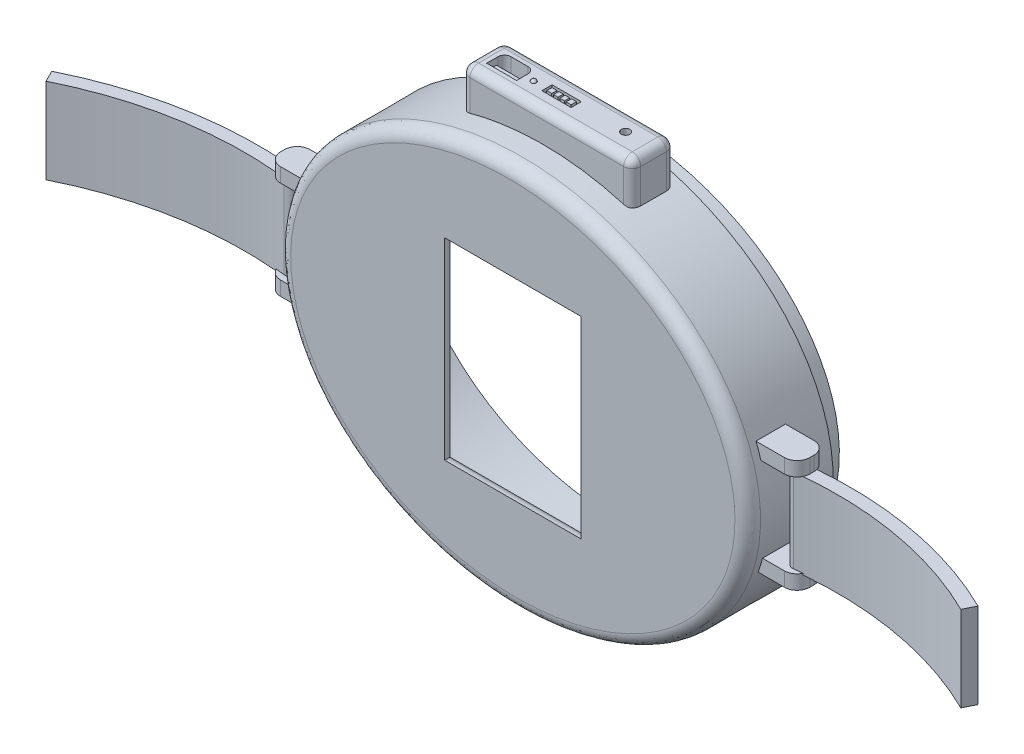
SolidWorks part; units mm, degrees
material "ABS"
ref_plane "Plan de face" through (0, 0, 0) normal (0, 0, 1) x (1, 0, 0)
ref_plane "Plan de dessus" through (0, 0, 0) normal (0, 1, 0) x (1, 0, 0)
ref_plane "Plan de droite" through (0, 0, 0) normal (1, 0, 0) x (0, 0, -1)
sketch "Esquisse1" plane through (0, 0, 0) normal (0, 0, 1) x (1, 0, 0)
  ellipse E0 centre (0, 0) end of major axis (55, -2.2067) minor radius 45.0362
  dimension "D1" = 110
  dimension "D2" = 90
extrude "Boss.-Extru.1" add sketch "Esquisse1" along normal blind 20
sketch "Esquisse2" plane through (0, 0, 0) normal (0, 0, -1) x (-1, 0, 0)
  ellipse E0 centre (0, 0) end of major axis (49.5, 0) minor radius 39.5
  dimension "D1" = 99
  dimension "D2" = 79
extrude "Enlèv. mat.-Extru.1" cut sketch "Esquisse2" against normal blind 17
sketch "Esquisse4" plane through (0, 0, 0) normal (0, 0, -1) x (-1, 0, 0)
  ellipse E0 centre (0, 0) end of major axis (49.5, 0) minor radius 39.5
  ellipse E1 centre (0, 0) end of major axis (49.5, 0) minor radius 39.5 construction
  ellipse E2 centre (0, 0) end of major axis (51.5, 0) minor radius 41.5
  dimension "D1" = 83
  dimension "D2" = 103
extrude "Boss.-Extru.2" add sketch "Esquisse4" along normal blind 5
sketch "Esquisse5" plane through (0, 0, 17) normal (0, 0, -1) x (-1, 0, 0)
  line L0 (-78.8633, 0) -> (101.9973, 0) construction
  line L1 (-15.9471, 22.5665) -> (15.9471, 22.5665)
  line L2 (-15.9471, 22.5665) -> (-15.9471, -22.5665)
  line L3 (-15.9471, -22.5665) -> (15.9471, -22.5665)
  line L4 (15.9471, 22.5665) -> (15.9471, -22.5665)
  line L5 (-15.9471, 22.5665) -> (15.9471, -22.5665) construction
  line L6 (-15.9471, -22.5665) -> (15.9471, 22.5665) construction
  point P0 (0, 0)
ref_plane "Plan1" through (0, -47.5, 0) normal (0, 1, 0) x (1, 0, 0)
ref_plane "Plan2" through (62, 0, 0) normal (1, 0, 0) x (0, 0, -1)
sketch "Esquisse7" plane through (62, 0, 0) normal (1, 0, 0) x (0, 0, -1)
  line L0 (0, 0) -> (-49.6576, 0) construction
  line L1 (-8.4829, -13.1626) -> (-15.4028, -13.1626)
  line L2 (-8.4829, -13.1626) -> (-8.4829, -9.8236)
  line L3 (-8.4829, -9.8236) -> (-15.4028, -9.8236)
  line L4 (-15.4028, -13.1626) -> (-15.4028, -9.8236)
  line L5 (-15.4028, 13.1626) -> (-15.4028, 9.8236)
  line L6 (-8.4829, 13.1626) -> (-15.4028, 13.1626)
  line L7 (-8.4829, 13.1626) -> (-8.4829, 9.8236)
  line L8 (-8.4829, 9.8236) -> (-15.4028, 9.8236)
extrude "Boss.-Extru.3" add sketch "Esquisse7" against normal blind 10
fillet "Congé2" radius 3 4 edges at (62, 11.4931, 15.4028) (62, 11.4931, 8.4829) (62, -11.4931, 8.4829) (62, -11.4931, 15.4028)
sketch "Esquisse8" plane through (0, 13.1626, 0) normal (0, 1, 0) x (1, 0, 0)
  line L0 (62, -11.9429) -> (50.9958, -11.9429) construction
  line L1 (62, -11.4829) -> (62, -12.4028) construction
  circle A1 centre (59.2821, -11.9429) radius 1
  dimension "D1" = 2
extrude "Boss.-Extru.4" add sketch "Esquisse8" against normal blind 25
mirror "Symétrie1" about plane through (0, 0, 0) normal (1, 0, 0) of "Boss.-Extru.4", "Boss.-Extru.3", "Congé2"
sketch "Esquisse9" plane through (0, 9.8236, 0) normal (0, -1, 0) x (-1, 0, 0)
  line L0 (-108.4769, -19.5088) -> (-107.145, -22.197)
  arc A0 (-59.2821, -10.9429) -> (-108.4769, -19.5088) centre (-69.4021, -98.3701) ccw
  circle A1 centre (-59.2821, -11.9429) radius 1 construction
  arc A2 (-59.627, -13.923) -> (-107.145, -22.197) centre (-69.4021, -98.3701) ccw
  arc A3 (-59.627, -13.923) -> (-59.2821, -10.9429) centre (-59.4546, -12.4329) ccw
  dimension "D1" = 3
extrude "Boss.-Extru.5" add sketch "Esquisse9" along normal blind 20
mirror "Symétrie2" about plane through (0, 0, 0) normal (1, 0, 0) of "Boss.-Extru.5"
extrude "Enlèv. mat.-Extru.2" cut sketch "Esquisse5" against normal through all
fillet "Congé3" radius 3 1 edges at (-49.5, 0, 17)
fillet "Congé4" radius 3 1 edges at (55, -2.2067, 20)
fillet "Congé5" radius 3 4 edges at (0, -22.5665, 17) (-15.9471, 0, 17) (15.9471, 0, 17) (0, 22.5665, 17)
ref_plane "Plan3" through (0, 52, 0) normal (0, 1, 0) x (1, 0, 0)
sketch "Esquisse10" plane through (0, 52, 0) normal (0, 1, 0) x (1, 0, 0)
  line L0 (0, 29.0079) -> (0, -90.2476) construction
  line L1 (-20, -12.029) -> (20, -12.029)
  line L2 (-20, -12.029) -> (-20, -2.029)
  line L3 (-20, -2.029) -> (20, -2.029)
  line L4 (20, -12.029) -> (20, -2.029)
  line L5 (-20, -12.029) -> (20, -2.029) construction
  line L6 (-20, -2.029) -> (20, -12.029) construction
  point P0 (0, -7.029)
  dimension "D1" = 40
  dimension "D2" = 10
extrude "Boss.-Extru.6" add sketch "Esquisse10" against normal blind 10
fillet "Congé8" radius 2 8 edges at (0, 52, 12.029) (20, 47, 12.029) (20, 52, 7.029) (20, 47, 2.029) (0, 52, 2.029) (-20, 52, 7.029) (-20, 47.1163, 12.029) (-20, 47.1163, 2.029)
sketch "Esquisse11" plane through (0, 52, 0) normal (0, 1, 0) x (1, 0, 0)
  line L0 (-18, -7.029) -> (22.5805, -7.029) construction
  line L1 (-18, -4.029) -> (-18, -10.029) construction
  line L3 (-17.0041, -4.9423) -> (-10.0041, -4.9423)
  line L4 (-17.0041, -4.9423) -> (-17.0041, -9.1156)
  line L5 (-17.0041, -9.1156) -> (-10.0041, -9.1156)
  line L6 (-10.0041, -4.9423) -> (-10.0041, -9.1156)
  line L7 (-17.0041, -4.9423) -> (-10.0041, -9.1156) construction
  line L8 (-17.0041, -9.1156) -> (-10.0041, -4.9423) construction
  point P4 (-13.5041, -7.029)
  dimension "D1" = 7
extrude "Enlèv. mat.-Extru.3" cut sketch "Esquisse11" against normal blind 6
sketch "Esquisse12" plane through (0, 46, 0) normal (0, 1, 0) x (1, 0, 0)
  line L0 (-17.0041, -9.1156) -> (-10.0041, -9.1156) construction
  line L1 (-10.4458, -7.3727) -> (-16.4605, -7.3727)
  line L2 (-10.4458, -7.3727) -> (-10.4458, -9.1156)
  line L3 (-10.4458, -9.1156) -> (-16.4605, -9.1156)
  line L4 (-16.4605, -7.3727) -> (-16.4605, -9.1156)
extrude "Boss.-Extru.7" add sketch "Esquisse12" along normal blind 5
sketch "Esquisse13" plane through (0, 0, 7.3727) normal (0, 0, -1) x (-1, 0, 0)
  line L0 (10.4458, 46) -> (16.4605, 46) construction
  line L1 (13.888, 46) -> (13.0092, 46)
  line L2 (13.888, 46) -> (13.888, 50.6099)
  line L4 (13.0092, 46) -> (13.0092, 50.6099)
  line L7 (11.9961, 46) -> (11.1216, 46)
  line L8 (11.9961, 46) -> (11.9961, 50.6099)
  line L10 (11.1216, 46) -> (11.1216, 50.6099)
  line L11 (14.9026, 46) -> (15.7847, 46)
  line L12 (14.9026, 46) -> (14.9026, 50.6099)
  line L14 (15.7847, 46) -> (15.7847, 50.6099)
  line L17 (15.7847, 50.6099) -> (14.9026, 50.6099)
  line L18 (13.888, 50.6099) -> (13.0092, 50.6099)
  line L19 (11.9961, 50.6099) -> (11.1216, 50.6099)
  point P9 (0, 0)
  point P10 (0, 0)
  point P16 (14.9026, 50.6099)
  point P18 (15.7847, 50.8113)
  point P19 (13.888, 50.6099)
  point P20 (13.0092, 50.6099)
  point P21 (11.9961, 50.6099)
  point P22 (11.1216, 51)
extrude "Boss.-Extru.8" add sketch "Esquisse13" along normal blind 0.5
chamfer "Chanfrein2" distance 2 angle 45 3 edges at (-11.5588, 50.6099, 6.8727) (-13.4486, 50.6099, 6.8727) (-15.3436, 50.6099, 6.8727)
fillet "Congé9" radius 1.5 2 edges at (-10.0041, 49, 4.9423) (-17.0041, 49, 4.9423)
sketch "Esquisse14" plane through (0, 52, 0) normal (0, 1, 0) x (1, 0, 0)
  line L0 (18, -7.029) -> (1.3064, -7.029) construction
  line L1 (-4.9633, -5.8292) -> (1.8764, -5.8292)
  line L2 (-4.9633, -5.8292) -> (-4.9633, -8.2288)
  line L3 (-4.9633, -8.2288) -> (1.8764, -8.2288)
  line L4 (1.8764, -5.8292) -> (1.8764, -8.2288)
  line L5 (18, -10.029) -> (18, -4.029) construction
  line L6 (-2.2851, -6.3991) -> (-2.2851, -8.5872) construction
  line L7 (-4.3933, -6.3991) -> (-3.236, -6.3991)
  line L8 (-4.3933, -6.3991) -> (-4.3933, -7.6588)
  line L9 (-4.3933, -7.6588) -> (-3.236, -7.6588)
  line L10 (1.3064, -6.3991) -> (1.3064, -7.6588)
  line L11 (-3.236, -6.3991) -> (-3.236, -7.6588)
  line L12 (-1.7527, -6.3991) -> (-1.7527, -7.6588)
  line L13 (-1.3342, -6.3991) -> (-1.3342, -7.6588)
  line L14 (-0.2694, -6.3991) -> (-0.2694, -7.6588)
  line L15 (0.1491, -6.3991) -> (0.1491, -7.6588)
  line L16 (-1.5434, -5.0733) -> (-1.5434, -5.8292) construction
  line L17 (-2.8175, -6.3991) -> (-2.8175, -7.6588)
  line L18 (-4.3933, -7.029) -> (-24.3422, -7.029) construction
  line L19 (-0.8018, -6.3991) -> (-0.8018, -8.5872) construction
  line L20 (-2.8175, -6.3991) -> (-1.7527, -6.3991)
  line L21 (-2.8175, -7.6588) -> (-1.7527, -7.6588)
  line L22 (-1.5434, -8.2288) -> (-1.5434, -12.8732) construction
  line L23 (-1.3342, -6.3991) -> (-0.2694, -6.3991)
  line L24 (-1.3342, -7.6588) -> (-0.2694, -7.6588)
  line L25 (0.1491, -6.3991) -> (1.3064, -6.3991)
  line L26 (0.1491, -7.6588) -> (1.3064, -7.6588)
  point P8 (-1.5434, -7.029)
extrude "Enlèv. mat.-Extru.4" cut sketch "Esquisse14" against normal blind 5
sketch "Esquisse15" plane through (0, 52, 0) normal (0, 1, 0) x (1, 0, 0)
  circle A0 centre (-7.8056, -7.2976) radius 0.6081
extrude "Boss.-Extru.9" add sketch "Esquisse15" along normal blind 0.5
fillet "Congé11" radius 0.6 1 edges at (-7.8056, 52.5, 7.9057)
sketch "Esquisse16" plane through (0, 52, 0) normal (0, 1, 0) x (1, 0, 0)
  circle A0 centre (13.1845, -6.7655) radius 1
  dimension "D1" = 2
extrude "Enlèv. mat.-Extru.5" cut sketch "Esquisse16" against normal blind 4
